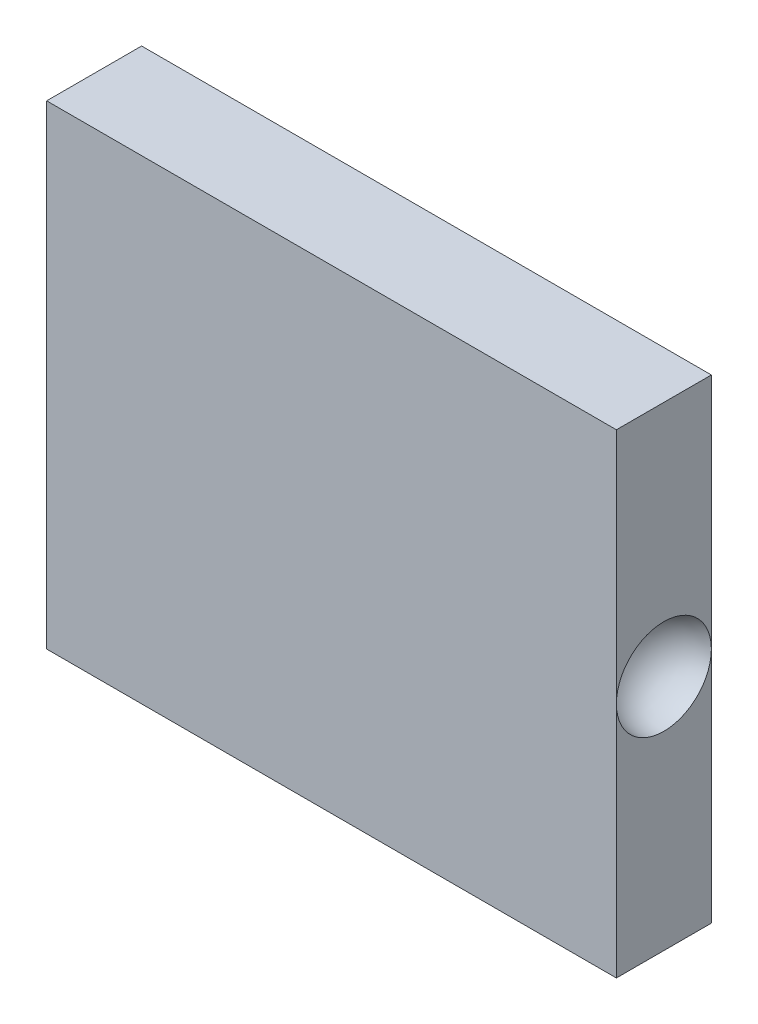
SolidWorks part; units mm, degrees
ref_plane "前视基准面" through (0, 0, 0) normal (0, 0, 1) x (1, 0, 0)
ref_plane "上视基准面" through (0, 0, 0) normal (0, 1, 0) x (1, 0, 0)
ref_plane "右视基准面" through (0, 0, 0) normal (1, 0, 0) x (0, 0, -1)
other "Configuration Table"
sketch "草图2" plane through (0, 0, 0) normal (0, 0, 1) x (1, 0, 0)
  line L1 (-30, 25) -> (30, 25)
  line L2 (-30, 25) -> (-30, -25)
  line L3 (-30, -25) -> (30, -25)
  line L4 (30, 25) -> (30, -25)
  line L5 (-30, 25) -> (30, -25) construction
  line L6 (-30, -25) -> (30, 25) construction
  point P0 (0, 0)
  dimension "D1" = 50
  dimension "D2" = 60
extrude "凸台-拉伸1" add sketch "草图2" along normal blind 10
sketch "草图5" plane through (0, 0, 0) normal (0, 1, 0) x (1, 0, 0)
  line L0 (-30, -10) -> (-30, 0) construction
  line L1 (-30, 0) -> (-30, -10)
  arc A0 (-30, -10) -> (-30, 0) centre (-30, -5) ccw
  dimension "D1" = 5
revolve "切除-旋转5" cut sketch "草图5" angle 360 about L1
mirror "镜向1" about plane through (0, 0, 0) normal (1, 0, 0) of "切除-旋转5"
sketch "草图6" plane through (0, 0, 0) normal (0, 1, 0) x (1, 0, 0)
  line L0 (-9.2, 0) -> (9.2, 0)
  arc A0 (-9.2, 0) -> (9.2, 0) centre (0, 0) ccw
  dimension "D1" = 9.2
revolve "切除-旋转6" cut sketch "草图6" angle 360 about L0
